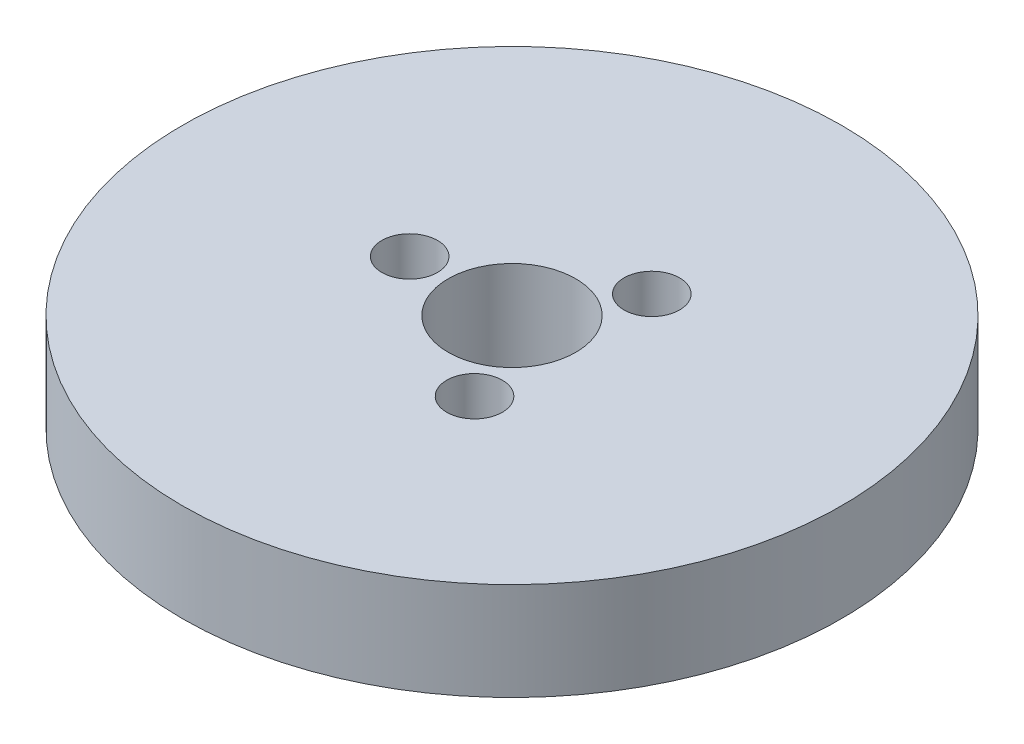
SolidWorks part; units mm, degrees
ref_plane "Front Plane" through (0, 0, 0) normal (0, 0, 1) x (1, 0, 0)
ref_plane "Top Plane" through (0, 0, 0) normal (0, 1, 0) x (1, 0, 0)
ref_plane "Right Plane" through (0, 0, 0) normal (1, 0, 0) x (0, 0, -1)
sketch "Sketch1" plane through (0, 0, 0) normal (0, 1, 0) x (1, 0, 0)
  circle A0 centre (0, 0) radius 77.5
  dimension "FLANGE_OD" = 155
extrude "Boss-Extrude1" add sketch "Sketch1" along normal blind 23
sketch "Sketch2" plane through (0, 0, 0) normal (0, 1, 0) x (1, 0, 0)
  circle A0 centre (0, 0) radius 15
  dimension "BORE_D" = 30
extrude "Cut-Extrude1" cut sketch "Sketch2" along normal through all
sketch "Sketch3" plane through (0, 23, 0) normal (0, 1, 0) x (1, 0, 0)
  circle A0 centre (0, 0) radius 24.0653 construction
  circle A1 centre (-24.0653, 0) radius 6.542
  dimension "BOLT_D" = 13.0841
  dimension "BOLT_PCD" = 48.1306
extrude "Cut-Extrude2" cut sketch "Sketch3" against normal blind 20.1765
pattern_circular "CirPattern1" count 3 over 360 about axis through (0, 0, 0) along (0, 1, 0) of "Cut-Extrude2"
